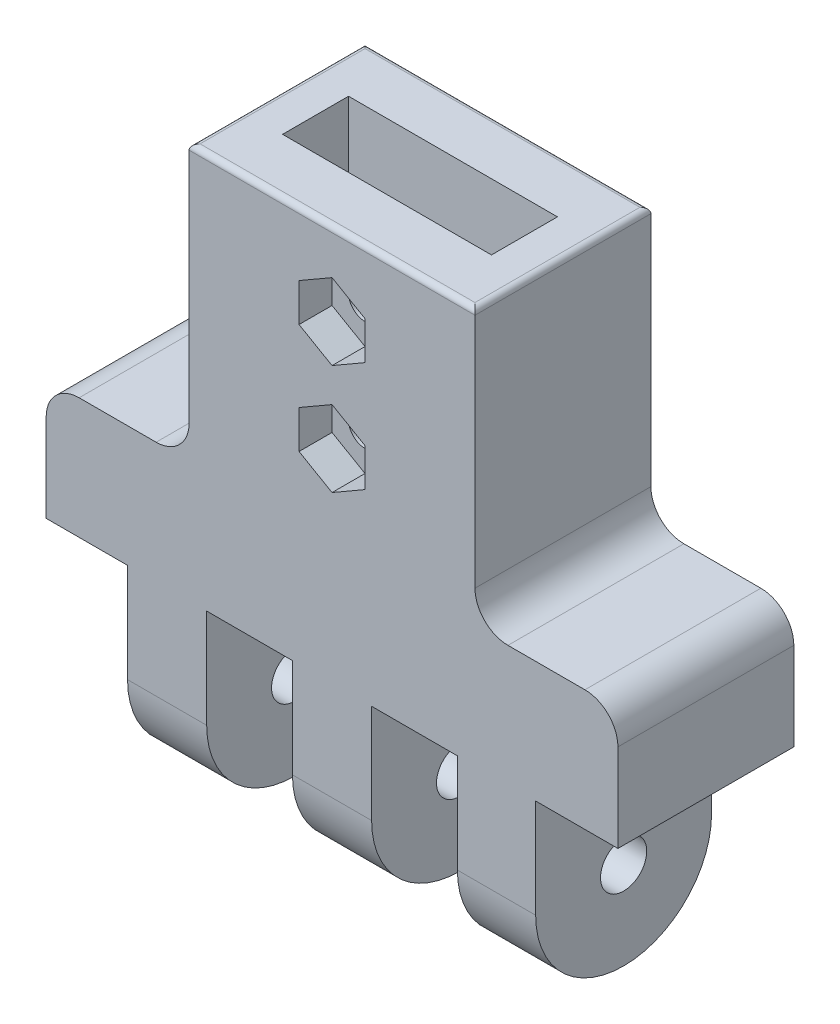
SolidWorks part; units mm, degrees
ref_plane "Front Plane" through (0, 0, 0) normal (0, 0, 1) x (1, 0, 0)
ref_plane "Top Plane" through (0, 0, 0) normal (0, 1, 0) x (1, 0, 0)
ref_plane "Right Plane" through (0, 0, 0) normal (1, 0, 0) x (0, 0, -1)
sketch "Sketch2" plane through (0, 0, 0) normal (1, 0, 0) x (0, 0, -1)
  line L2 (-8, 0) -> (-8, 20)
  line L3 (-8, 20) -> (8, 20)
  line L4 (8, 0) -> (8, 20)
  circle A0 centre (0, 0) radius 2.1
  arc A1 (-8, 0) -> (8, 0) centre (0, 0) ccw
  dimension "D1" = 16
  dimension "D2" = 4.2
  dimension "D3" = 20
extrude "Boss-Extrude1" add sketch "Sketch2" along normal mid plane 52
sketch "Sketch3" plane through (0, 0, 8) normal (0, 0, 1) x (1, 0, 0)
  line L0 (26, 0) -> (-26, 0) construction
  line L1 (-26, -9) -> (-18.6, -9)
  line L2 (-26, -9) -> (-26, 9)
  line L3 (-26, 9) -> (-18.6, 9)
  line L4 (-18.6, -9) -> (-18.6, 9)
  line L5 (-26, -9) -> (-18.6, 9) construction
  line L6 (-26, 9) -> (-18.6, -9) construction
  line L8 (-11.4, -9) -> (-3.6, -9)
  line L9 (-11.4, -9) -> (-11.4, 9)
  line L10 (-11.4, 9) -> (-3.6, 9)
  line L11 (-3.6, -9) -> (-3.6, 9)
  line L12 (-11.4, -9) -> (-3.6, 9) construction
  line L13 (-11.4, 9) -> (-3.6, -9) construction
  line L14 (3.6, -9) -> (11.4, -9)
  line L15 (3.6, -9) -> (3.6, 9)
  line L16 (3.6, 9) -> (11.4, 9)
  line L17 (11.4, -9) -> (11.4, 9)
  line L18 (3.6, -9) -> (11.4, 9) construction
  line L19 (3.6, 9) -> (11.4, -9) construction
  line L20 (-26, 20) -> (-26, 0) construction
  line L21 (26, 20) -> (26, 0) construction
  line L22 (18.519, -9) -> (26, -9)
  line L23 (18.519, -9) -> (18.519, 9)
  line L24 (18.519, 9) -> (26, 9)
  line L25 (26, -9) -> (26, 9)
  line L26 (18.519, -9) -> (26, 9) construction
  line L27 (18.519, 9) -> (26, -9) construction
  point P0 (-22.3, 0)
  point P7 (-7.5, 0)
  point P12 (7.5, 0)
  point P17 (-22.3, 9)
  point P20 (22.2595, 0)
  dimension "D1" = 9
  dimension "D4" = 7.2
  dimension "D6" = 7.2
  dimension "D2" = 7.8
  dimension "D3" = 14.6
extrude "Cut-Extrude1" cut sketch "Sketch3" against normal through all
ref_plane "Plane1" through (0, 20, 0) normal (0, 1, 0) x (1, 0, 0)
sketch "Sketch4" plane through (0, 20, 0) normal (0, 1, 0) x (1, 0, 0)
  line L0 (26, 8) -> (26, -8) construction
  line L1 (13, -8) -> (-13, -8)
  line L2 (13, -8) -> (13, 8)
  line L3 (13, 8) -> (-13, 8)
  line L4 (-13, -8) -> (-13, 8)
  line L5 (13, -8) -> (-13, 8) construction
  line L6 (13, 8) -> (-13, -8) construction
  line L8 (26, -8) -> (-26, -8) construction
  point P0 (0, 0)
  dimension "D1" = 26
  dimension "D2" = 16
  dimension "D3" = 26
extrude "Boss-Extrude2" add sketch "Sketch4" along normal blind 25
ref_plane "Plane2" through (0, 45, 0) normal (0, 1, 0) x (1, 0, 0)
sketch "Sketch5" plane through (0, 45, 0) normal (0, 1, 0) x (1, 0, 0)
  line L0 (13, -8) -> (13, 8) construction
  line L1 (-9.5, 3) -> (9.5, 3)
  line L2 (-9.5, 3) -> (-9.5, -3)
  line L3 (-9.5, -3) -> (9.5, -3)
  line L4 (9.5, 3) -> (9.5, -3)
  line L5 (-9.5, 3) -> (9.5, -3) construction
  line L6 (-9.5, -3) -> (9.5, 3) construction
  line L8 (-13, -8) -> (13, -8) construction
  line L10 (13, 8) -> (-13, 8) construction
  line L11 (13, -8) -> (13, 8) construction
  line L12 (-13, 8) -> (-13, -8) construction
  point P0 (0, 0)
  dimension "D1" = 19
  dimension "D2" = 13
  dimension "D3" = 6
  dimension "D4" = 5
  dimension "D5" = 5
extrude "Cut-Extrude2" cut sketch "Sketch5" against normal blind 25
fillet "Fillet2" radius 3 2 edges at (26, 20, 0) (-26, 20, 0)
sketch "Sketch6" plane through (0, 0, 0) normal (0, 0, 1) x (1, 0, 0)
  line L0 (9.5, 20) -> (9.5, 45) construction
  line L1 (-16.3932, 32.5) -> (15.2785, 32.5) construction
  line L2 (9.5, 20) -> (-9.5, 20) construction
  circle A0 centre (0, 37.5) radius 1.5
  circle A1 centre (0, 27.5) radius 1.5
  dimension "D1" = 3
  dimension "D2" = 9.5
  dimension "D3" = 10
  dimension "D4" = 5
  dimension "D5" = 12.5
extrude "Cut-Extrude3" cut sketch "Sketch6" against normal mid plane 25
fillet "Fillet3" radius 0.5 4 edges at (0, 45, 8) (13, 45, 0) (0, 45, -8) (-13, 45, 0)
fillet "Fillet4" radius 3 2 edges at (13, 20, 0) (-13, 20, 0)
ref_plane "Plane3" through (0, 0, 8) normal (0, 0, 1) x (1, 0, 0)
sketch "Sketch7" plane through (0, 0, 8) normal (0, 0, 1) x (1, 0, 0)
  line L1 (3, 35.7679) -> (3, 39.2321)
  line L2 (3, 39.2321) -> (0, 40.9641)
  line L3 (0, 40.9641) -> (-3, 39.2321)
  line L4 (-3, 39.2321) -> (-3, 35.7679)
  line L5 (-3, 35.7679) -> (0, 34.0359)
  line L6 (0, 34.0359) -> (3, 35.7679)
  line L7 (3, 25.7679) -> (3, 29.2321)
  line L8 (3, 29.2321) -> (0, 30.9641)
  line L9 (0, 30.9641) -> (-3, 29.2321)
  line L10 (-3, 29.2321) -> (-3, 25.7679)
  line L11 (-3, 25.7679) -> (0, 24.0359)
  line L12 (0, 24.0359) -> (3, 25.7679)
  circle A0 centre (0, 37.5) radius 3 construction
  circle A1 centre (0, 27.5) radius 3 construction
  circle A2 centre (0, 27.5) radius 1.5 construction
  point P10 (0, 0)
  dimension "D1" = 6
  dimension "D2" = 6
extrude "Cut-Extrude4" cut sketch "Sketch7" against normal blind 3
equation "\"hingewidth\"=7.2"
equation "\"fingerwidth\"=10.5"
equation "\"gapwidth\"=7.4"
equation "\"D4@Sketch3\"=\"hingewidth\""
equation "\"D6@Sketch3\"=\"hingewidth\""
